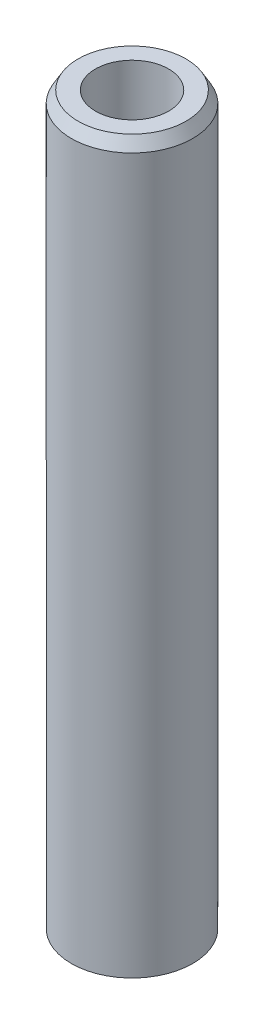
SolidWorks part; units mm, degrees
ref_plane "Front Plane" through (0, 0, 0) normal (0, 0, 1) x (1, 0, 0)
ref_plane "Top Plane" through (0, 0, 0) normal (0, 1, 0) x (1, 0, 0)
ref_plane "Right Plane" through (0, 0, 0) normal (1, 0, 0) x (0, 0, -1)
sketch "Sketch1" plane through (0, 0, 0) normal (0, 1, 0) x (1, 0, 0)
  circle A0 centre (0, 0) radius 10
  dimension "SHAFT_OD" = 20
extrude "Boss-Extrude1" add sketch "Sketch1" along normal blind 120.7032
sketch "Sketch2" plane through (0, 0, 0) normal (0, 1, 0) x (1, 0, 0)
  circle A0 centre (0, 0) radius 6.0259
  dimension "BORE_D" = 12.0518
extrude "Cut-Extrude1" cut sketch "Sketch2" along normal through all
chamfer "Chamfer1" distance 1.9149 angle 30 2 edges at (0, 120.7032, 10) (0, 0, 10) first distance on face at (0, 120.7032, 10) first distance on face at (0, 0, 6.0259)
